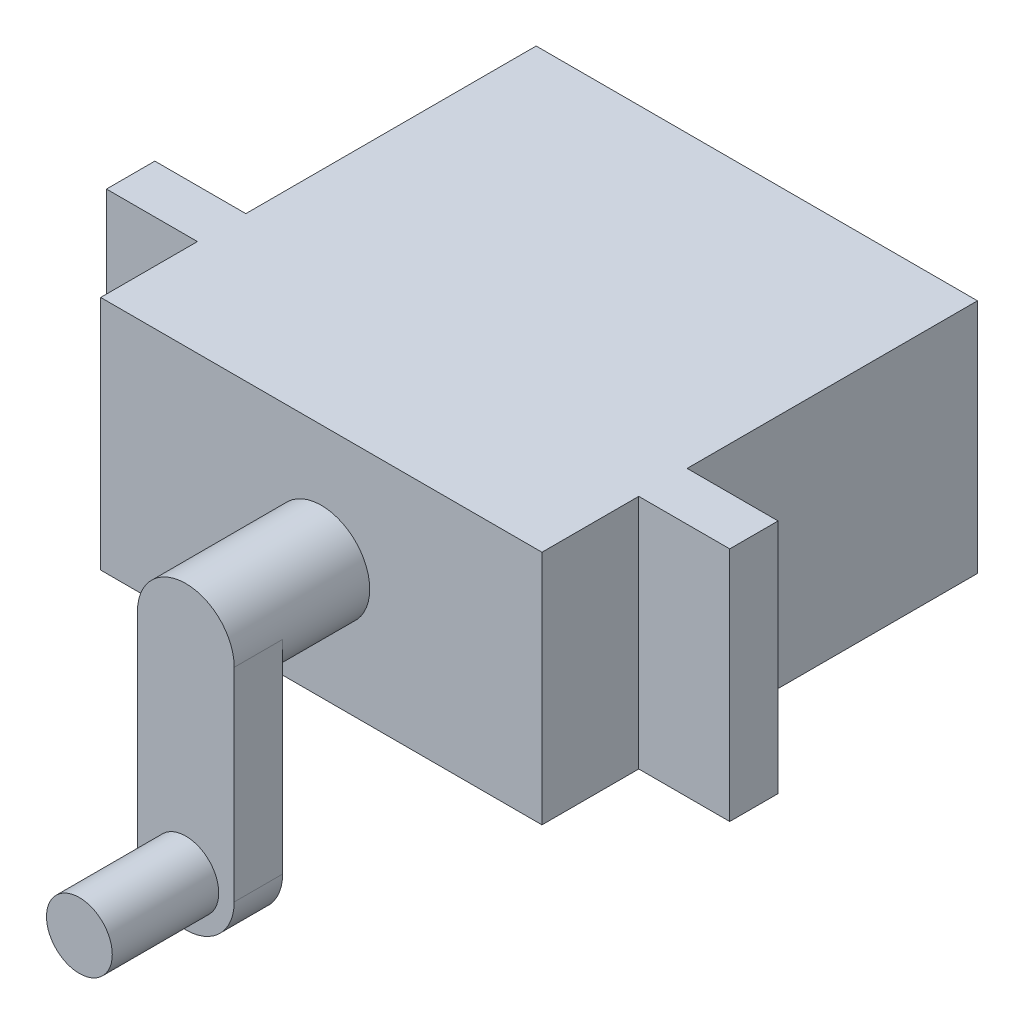
SolidWorks part; units mm, degrees
ref_plane "Plan de face" through (0, 0, 0) normal (0, 0, 1) x (1, 0, 0)
ref_plane "Plan de dessus" through (0, 0, 0) normal (0, 1, 0) x (1, 0, 0)
ref_plane "Plan de droite" through (0, 0, 0) normal (1, 0, 0) x (0, 0, -1)
sketch "Esquisse1" plane through (0, 0, 0) normal (0, 0, 1) x (1, 0, 0)
  line L1 (-11.4, 36.9) -> (11.4, 36.9)
  line L2 (-11.4, 36.9) -> (-11.4, 49.1)
  line L3 (-11.4, 49.1) -> (11.4, 49.1)
  line L4 (11.4, 36.9) -> (11.4, 49.1)
extrude "Corps_SG90" add sketch "Esquisse1" against normal blind 22.5 from offset 17 offset against normal yes
sketch "Esquisse2" plane through (0, 0, 0) normal (0, 0, 1) x (1, 0, 0)
  line L1 (-16.1, 36.9) -> (16.1, 36.9)
  line L2 (-16.1, 36.9) -> (-16.1, 49.1)
  line L3 (-16.1, 49.1) -> (16.1, 49.1)
  line L4 (16.1, 36.9) -> (16.1, 49.1)
extrude "Pattes_fixation" add sketch "Esquisse2" against normal blind 2.5 from offset 22 offset against normal yes
sketch "Esquisse3" plane through (0, 0, 0) normal (0, 0, 1) x (1, 0, 0)
  circle A0 centre (0, 43) radius 2.5
extrude "Axe_servo" add sketch "Esquisse3" against normal blind 4.5 from offset 12.5 offset against normal yes
sketch "Esquisse4" plane through (0, 0, 0) normal (0, 0, 1) x (1, 0, 0)
  line L0 (-2.5, 32.5) -> (-2.5, 43)
  line L1 (2.5, 43) -> (2.5, 32.5)
  arc A0 (-2.5, 43) -> (2.5, 43) centre (0, 43) cw
  arc A1 (2.5, 32.5) -> (-2.5, 32.5) centre (0, 32.5) cw
extrude "Palonnier_point_mort_bas" add sketch "Esquisse4" against normal blind 2.5 from offset 10 offset against normal yes
sketch "Esquisse5" plane through (0, 0, 0) normal (0, 0, 1) x (1, 0, 0)
  circle A0 centre (0, 32.5) radius 1.7
extrude "Ergot_entrainement" add sketch "Esquisse5" against normal blind 5.5 from offset 4.5 offset against normal yes
